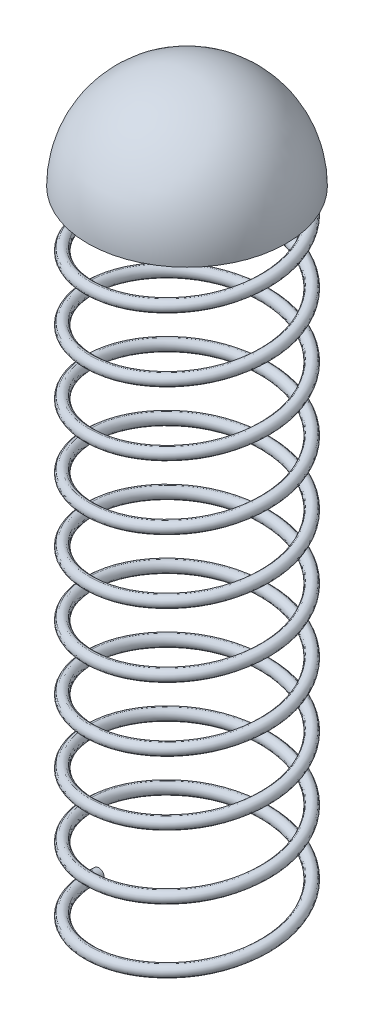
SolidWorks part; units mm, degrees
ref_plane "Front Plane" through (0, 0, 0) normal (0, 0, 1) x (1, 0, 0)
ref_plane "Top Plane" through (0, 0, 0) normal (0, 1, 0) x (1, 0, 0)
ref_plane "Right Plane" through (0, 0, 0) normal (1, 0, 0) x (0, 0, -1)
sketch "Sketch2" plane through (0, 0, 0) normal (0, 1, 0) x (1, 0, 0)
  circle A0 centre (0, 0) radius 2
  dimension "D1" = 4
curve "Helix/Spiral1" pitch 1.45 height 14.5 radius 2 centre (0, 0, 0) axis (0, 1, 0) start towards (0, 0, 1)
sketch "Sketch3" plane through (0, 0, 0) normal (0, 0, 1) x (1, 0, 0)
  circle A0 centre (-2, 0) radius 0.125
  spline S0 degree 3 poles (-2, 0) (-2, 0.03) (-1.8959, 0.0907) (-1.451, 0.1812) (-0.7853, 0.2719) (0, 0.3625) (0.7853, 0.4531) (1.451, 0.5437) (1.8959, 0.6344) (2.0521, 0.725) (1.8959, 0.8156) (1.451, 0.9062) (0.5634, 1.0271) (-0.5634, 1.1479) (-1.451, 1.2687) (-1.8959, 1.3594) (-2.0521, 1.45) (-1.8959, 1.5406) (-1.451, 1.6312) (-0.5634, 1.7521) (0.5634, 1.8729) (1.451, 1.9938) (1.8959, 2.0844) (2.0521, 2.175) (1.8959, 2.2656) (1.451, 2.3563) (0.5634, 2.4771) (-0.5634, 2.5979) (-1.451, 2.7188) (-1.8959, 2.8094) (-2.0521, 2.9) (-1.8959, 2.9906) (-1.451, 3.0812) (-0.5634, 3.2021) (0.5634, 3.3229) (1.451, 3.4437) (1.8959, 3.5344) (2.0521, 3.625) (1.8959, 3.7156) (1.451, 3.8062) (0.5634, 3.9271) (-0.5634, 4.0479) (-1.451, 4.1688) (-1.8959, 4.2594) (-2.0521, 4.35) (-1.8959, 4.4406) (-1.451, 4.5313) (-0.5634, 4.6521) (0.5634, 4.7729) (1.451, 4.8938) (1.8959, 4.9844) (2.0521, 5.075) (1.8959, 5.1656) (1.451, 5.2563) (0.5634, 5.3771) (-0.5634, 5.4979) (-1.451, 5.6188) (-1.8959, 5.7094) (-2.0521, 5.8) (-1.8959, 5.8906) (-1.451, 5.9813) (-0.5634, 6.1021) (0.5634, 6.2229) (1.451, 6.3438) (1.8959, 6.4344) (2.0521, 6.525) (1.8959, 6.6156) (1.451, 6.7063) (0.5634, 6.8271) (-0.5634, 6.9479) (-1.451, 7.0688) (-1.8959, 7.1594) (-2.0521, 7.25) (-1.8959, 7.3406) (-1.451, 7.4313) (-0.5634, 7.5521) (0.5634, 7.6729) (1.451, 7.7938) (1.8959, 7.8844) (2.0521, 7.975) (1.8959, 8.0656) (1.451, 8.1563) (0.5634, 8.2771) (-0.5634, 8.3979) (-1.451, 8.5188) (-1.8959, 8.6094) (-2.0521, 8.7) (-1.8959, 8.7906) (-1.451, 8.8813) (-0.5634, 9.0021) (0.5634, 9.1229) (1.451, 9.2438) (1.8959, 9.3344) (2.0521, 9.425) (1.8959, 9.5156) (1.451, 9.6063) (0.5634, 9.7271) (-0.5634, 9.8479) (-1.451, 9.9688) (-1.8959, 10.0594) (-2.0521, 10.15) (-1.8959, 10.2406) (-1.451, 10.3313) (-0.5634, 10.4521) (0.5634, 10.5729) (1.451, 10.6938) (1.8959, 10.7844) (2.0521, 10.875) (1.8959, 10.9656) (1.451, 11.0563) (0.5634, 11.1771) (-0.5634, 11.2979) (-1.451, 11.4188) (-1.8959, 11.5094) (-2.0521, 11.6) (-1.8959, 11.6906) (-1.451, 11.7813) (-0.5634, 11.9021) (0.5634, 12.0229) (1.451, 12.1438) (1.8959, 12.2344) (2.0521, 12.325) (1.8959, 12.4156) (1.451, 12.5063) (0.5634, 12.6271) (-0.5634, 12.7479) (-1.451, 12.8688) (-1.8959, 12.9594) (-2.0521, 13.05) (-1.8959, 13.1406) (-1.451, 13.2313) (-0.5634, 13.3521) (0.5634, 13.4729) (1.451, 13.5938) (1.8959, 13.6844) (2.0521, 13.775) (1.8959, 13.8656) (1.451, 13.9563) (0.7853, 14.0469) (0, 14.1375) (-0.7853, 14.2281) (-1.451, 14.3188) (-1.8959, 14.4093) (-2, 14.47) (-2, 14.5) knots 0 0 0 0 0.00625 0.0125 0.01875 0.025 0.03125 0.0375 0.04375 0.05 0.05625 0.0625 0.06875 0.08125 0.0875 0.09375 0.1 0.10625 0.1125 0.11875 0.13125 0.1375 0.14375 0.15 0.15625 0.1625 0.16875 0.18125 0.1875 0.19375 0.2 0.20625 0.2125 0.21875 0.23125 0.2375 0.24375 0.25 0.25625 0.2625 0.26875 0.28125 0.2875 0.29375 0.3 0.30625 0.3125 0.31875 0.33125 0.3375 0.34375 0.35 0.35625 0.3625 0.36875 0.38125 0.3875 0.39375 0.4 0.40625 0.4125 0.41875 0.43125 0.4375 0.44375 0.45 0.45625 0.4625 0.46875 0.48125 0.4875 0.49375 0.5 0.50625 0.5125 0.51875 0.53125 0.5375 0.54375 0.55 0.55625 0.5625 0.56875 0.58125 0.5875 0.59375 0.6 0.60625 0.6125 0.61875 0.63125 0.6375 0.64375 0.65 0.65625 0.6625 0.66875 0.68125 0.6875 0.69375 0.7 0.70625 0.7125 0.71875 0.73125 0.7375 0.74375 0.75 0.75625 0.7625 0.76875 0.78125 0.7875 0.79375 0.8 0.80625 0.8125 0.81875 0.83125 0.8375 0.84375 0.85 0.85625 0.8625 0.86875 0.88125 0.8875 0.89375 0.9 0.90625 0.9125 0.91875 0.93125 0.9375 0.94375 0.95 0.95625 0.9625 0.96875 0.975 0.98125 0.9875 0.99375 1 1 1 1 construction
  dimension "D2" = 0.25
  dimension "D1" = 2
sweep "Sweep1" add profiles "Sketch3" path "Helix/Spiral1"
sketch "Sketch4" plane through (0, 0, 0) normal (0, 0, 1) x (1, 0, 0)
  line L0 (-2.25, 14.5) -> (0, 14.5)
  line L1 (0, 14.5) -> (0, 16.75)
  arc A0 (0, 16.75) -> (-2.25, 14.5) centre (0, 14.5) ccw
  circle A2 centre (-2, 14.5) radius 0.125 construction
  spline S0 degree 3 poles (-2, 0) (-2, 0.03) (-1.8959, 0.0907) (-1.451, 0.1812) (-0.7853, 0.2719) (0, 0.3625) (0.7853, 0.4531) (1.451, 0.5437) (1.8959, 0.6344) (2.0521, 0.725) (1.8959, 0.8156) (1.451, 0.9062) (0.5634, 1.0271) (-0.5634, 1.1479) (-1.451, 1.2687) (-1.8959, 1.3594) (-2.0521, 1.45) (-1.8959, 1.5406) (-1.451, 1.6312) (-0.5634, 1.7521) (0.5634, 1.8729) (1.451, 1.9938) (1.8959, 2.0844) (2.0521, 2.175) (1.8959, 2.2656) (1.451, 2.3563) (0.5634, 2.4771) (-0.5634, 2.5979) (-1.451, 2.7188) (-1.8959, 2.8094) (-2.0521, 2.9) (-1.8959, 2.9906) (-1.451, 3.0812) (-0.5634, 3.2021) (0.5634, 3.3229) (1.451, 3.4437) (1.8959, 3.5344) (2.0521, 3.625) (1.8959, 3.7156) (1.451, 3.8062) (0.5634, 3.9271) (-0.5634, 4.0479) (-1.451, 4.1688) (-1.8959, 4.2594) (-2.0521, 4.35) (-1.8959, 4.4406) (-1.451, 4.5313) (-0.5634, 4.6521) (0.5634, 4.7729) (1.451, 4.8938) (1.8959, 4.9844) (2.0521, 5.075) (1.8959, 5.1656) (1.451, 5.2563) (0.5634, 5.3771) (-0.5634, 5.4979) (-1.451, 5.6188) (-1.8959, 5.7094) (-2.0521, 5.8) (-1.8959, 5.8906) (-1.451, 5.9813) (-0.5634, 6.1021) (0.5634, 6.2229) (1.451, 6.3438) (1.8959, 6.4344) (2.0521, 6.525) (1.8959, 6.6156) (1.451, 6.7063) (0.5634, 6.8271) (-0.5634, 6.9479) (-1.451, 7.0688) (-1.8959, 7.1594) (-2.0521, 7.25) (-1.8959, 7.3406) (-1.451, 7.4313) (-0.5634, 7.5521) (0.5634, 7.6729) (1.451, 7.7938) (1.8959, 7.8844) (2.0521, 7.975) (1.8959, 8.0656) (1.451, 8.1563) (0.5634, 8.2771) (-0.5634, 8.3979) (-1.451, 8.5188) (-1.8959, 8.6094) (-2.0521, 8.7) (-1.8959, 8.7906) (-1.451, 8.8813) (-0.5634, 9.0021) (0.5634, 9.1229) (1.451, 9.2438) (1.8959, 9.3344) (2.0521, 9.425) (1.8959, 9.5156) (1.451, 9.6063) (0.5634, 9.7271) (-0.5634, 9.8479) (-1.451, 9.9688) (-1.8959, 10.0594) (-2.0521, 10.15) (-1.8959, 10.2406) (-1.451, 10.3313) (-0.5634, 10.4521) (0.5634, 10.5729) (1.451, 10.6938) (1.8959, 10.7844) (2.0521, 10.875) (1.8959, 10.9656) (1.451, 11.0563) (0.5634, 11.1771) (-0.5634, 11.2979) (-1.451, 11.4188) (-1.8959, 11.5094) (-2.0521, 11.6) (-1.8959, 11.6906) (-1.451, 11.7813) (-0.5634, 11.9021) (0.5634, 12.0229) (1.451, 12.1438) (1.8959, 12.2344) (2.0521, 12.325) (1.8959, 12.4156) (1.451, 12.5063) (0.5634, 12.6271) (-0.5634, 12.7479) (-1.451, 12.8688) (-1.8959, 12.9594) (-2.0521, 13.05) (-1.8959, 13.1406) (-1.451, 13.2313) (-0.5634, 13.3521) (0.5634, 13.4729) (1.451, 13.5938) (1.8959, 13.6844) (2.0521, 13.775) (1.8959, 13.8656) (1.451, 13.9563) (0.7853, 14.0469) (0, 14.1375) (-0.7853, 14.2281) (-1.451, 14.3188) (-1.8959, 14.4093) (-2, 14.47) (-2, 14.5) knots 0 0 0 0 0.00625 0.0125 0.01875 0.025 0.03125 0.0375 0.04375 0.05 0.05625 0.0625 0.06875 0.08125 0.0875 0.09375 0.1 0.10625 0.1125 0.11875 0.13125 0.1375 0.14375 0.15 0.15625 0.1625 0.16875 0.18125 0.1875 0.19375 0.2 0.20625 0.2125 0.21875 0.23125 0.2375 0.24375 0.25 0.25625 0.2625 0.26875 0.28125 0.2875 0.29375 0.3 0.30625 0.3125 0.31875 0.33125 0.3375 0.34375 0.35 0.35625 0.3625 0.36875 0.38125 0.3875 0.39375 0.4 0.40625 0.4125 0.41875 0.43125 0.4375 0.44375 0.45 0.45625 0.4625 0.46875 0.48125 0.4875 0.49375 0.5 0.50625 0.5125 0.51875 0.53125 0.5375 0.54375 0.55 0.55625 0.5625 0.56875 0.58125 0.5875 0.59375 0.6 0.60625 0.6125 0.61875 0.63125 0.6375 0.64375 0.65 0.65625 0.6625 0.66875 0.68125 0.6875 0.69375 0.7 0.70625 0.7125 0.71875 0.73125 0.7375 0.74375 0.75 0.75625 0.7625 0.76875 0.78125 0.7875 0.79375 0.8 0.80625 0.8125 0.81875 0.83125 0.8375 0.84375 0.85 0.85625 0.8625 0.86875 0.88125 0.8875 0.89375 0.9 0.90625 0.9125 0.91875 0.93125 0.9375 0.94375 0.95 0.95625 0.9625 0.96875 0.975 0.98125 0.9875 0.99375 1 1 1 1 construction
  dimension "D1" = 4.5
revolve "Revolve2" add sketch "Sketch4" angle 360 about L1
